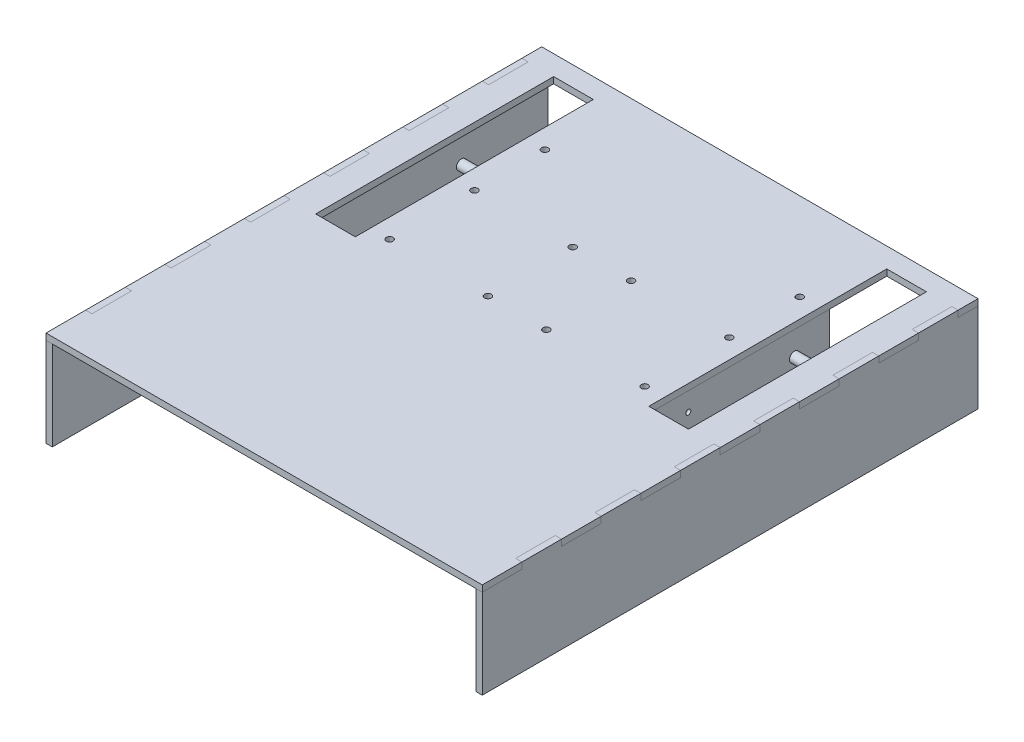
SolidWorks part; units mm, degrees
ref_plane "Front Plane" through (0, 0, 0) normal (0, 0, 1) x (1, 0, 0)
ref_plane "Top Plane" through (0, 0, 0) normal (0, 1, 0) x (1, 0, 0)
ref_plane "Right Plane" through (0, 0, 0) normal (1, 0, 0) x (0, 0, -1)
sketch "Sketch2" plane through (0, 0, 0) normal (0, 1, 0) x (1, 0, 0)
  line L7 (-162.2662, -88.2141) -> (57.7338, -88.2141)
  line L8 (21.7338, 151.7859) -> (41.7338, 151.7859)
  line L9 (57.7338, -88.2141) -> (57.7338, -68.2141)
  line L10 (57.7338, -68.2141) -> (54.5588, -68.2141)
  line L11 (54.5588, -68.2141) -> (54.5588, -48.2141)
  line L12 (54.5588, -48.2141) -> (57.7338, -48.2141)
  line L13 (-162.2662, -88.2141) -> (-162.2662, -68.2141)
  line L14 (-162.2662, -68.2141) -> (-159.0912, -68.2141)
  line L15 (-159.0912, -68.2141) -> (-159.0912, -48.2141)
  line L16 (-159.0912, -48.2141) -> (-162.2662, -48.2141)
  line L17 (-162.2662, -48.2141) -> (-162.2662, -28.2141)
  line L18 (-162.2662, -28.2141) -> (-159.0912, -28.2141)
  line L19 (-159.0912, -28.2141) -> (-159.0912, -8.2141)
  line L20 (-159.0912, -8.2141) -> (-162.2662, -8.2141)
  line L21 (57.7338, -28.2141) -> (54.5588, -28.2141)
  line L22 (54.5588, -28.2141) -> (54.5588, -8.2141)
  line L23 (54.5588, -8.2141) -> (57.7338, -8.2141)
  line L24 (57.7338, -48.2141) -> (57.7338, -28.2141)
  line L25 (-162.2662, -8.2141) -> (-162.2662, 11.7859)
  line L26 (-162.2662, 11.7859) -> (-159.0912, 11.7859)
  line L27 (-159.0912, 11.7859) -> (-159.0912, 31.7859)
  line L28 (-159.0912, 31.7859) -> (-162.2662, 31.7859)
  line L29 (57.7338, 11.7859) -> (54.5588, 11.7859)
  line L30 (54.5588, 11.7859) -> (54.5588, 31.7859)
  line L31 (54.5588, 31.7859) -> (57.7338, 31.7859)
  line L32 (57.7338, -8.2141) -> (57.7338, 11.7859)
  line L33 (-162.2662, 31.7859) -> (-162.2662, 51.7859)
  line L34 (-162.2662, 51.7859) -> (-159.0912, 51.7859)
  line L35 (-159.0912, 51.7859) -> (-159.0912, 71.7859)
  line L36 (-159.0912, 71.7859) -> (-162.2662, 71.7859)
  line L37 (57.7338, 51.7859) -> (54.5588, 51.7859)
  line L38 (54.5588, 51.7859) -> (54.5588, 71.7859)
  line L39 (54.5588, 71.7859) -> (57.7338, 71.7859)
  line L40 (57.7338, 31.7859) -> (57.7338, 51.7859)
  line L45 (21.7338, 151.7859) -> (21.7338, 31.7859)
  line L46 (21.7338, 31.7859) -> (41.7338, 31.7859)
  line L47 (41.7338, 151.7859) -> (41.7338, 31.7859)
  line L48 (-146.2662, 151.7859) -> (-126.2662, 151.7859)
  line L49 (-146.2662, 151.7859) -> (-146.2662, 31.7859)
  line L50 (-146.2662, 31.7859) -> (-126.2662, 31.7859)
  line L51 (-126.2662, 151.7859) -> (-126.2662, 31.7859)
  line L52 (-162.2662, 71.7859) -> (-162.2662, 91.7859)
  line L53 (-162.2662, 91.7859) -> (-159.0912, 91.7859)
  line L54 (-159.0912, 91.7859) -> (-159.0912, 111.7859)
  line L55 (-159.0912, 111.7859) -> (-162.2662, 111.7859)
  line L56 (57.7338, 91.7859) -> (54.5588, 91.7859)
  line L57 (54.5588, 91.7859) -> (54.5588, 111.7859)
  line L58 (54.5588, 111.7859) -> (57.7338, 111.7859)
  line L59 (57.7338, 71.7859) -> (57.7338, 91.7859)
  line L63 (-162.2662, 111.7859) -> (-162.2662, 131.7859)
  line L64 (-162.2662, 131.7859) -> (-159.0912, 131.7859)
  line L65 (-159.0912, 131.7859) -> (-159.0912, 151.7859)
  line L66 (-159.0912, 151.7859) -> (-162.2662, 151.7859)
  line L67 (57.7338, 131.7859) -> (54.5588, 131.7859)
  line L68 (54.5588, 131.7859) -> (54.5588, 151.7859)
  line L69 (54.5588, 151.7859) -> (57.7338, 151.7859)
  line L70 (57.7338, 111.7859) -> (57.7338, 131.7859)
  line L71 (57.7338, 151.7859) -> (57.7338, 161.7859)
  line L72 (57.7338, 161.7859) -> (-162.2662, 161.7859)
  line L73 (-162.2662, 161.7859) -> (-162.2662, 151.7859)
  dimension "D1" = 3.175
  dimension "D2" = 20
  dimension "D3" = 20
  dimension "D4" = 3.175
  dimension "D6" = 220
  dimension "D8" = 20
  dimension "D9" = 20
  dimension "D10" = 16
  dimension "D11" = 16
  dimension "D13" = 120
  dimension "D7" = 10
  dimension "D12" = 10
  dimension "D5" = 6
extrude "Boss-Extrude1" add sketch "Sketch2" along normal blind 3.175
ref_plane "Plane3" through (-52.2662, 0, 0) normal (-1, 0, 0) x (0, 0, 1)
sketch "Sketch3" plane through (-159.0912, 0, 0) normal (-1, 0, 0) x (0, 0, 1)
  line L0 (68.2141, 3.175) -> (68.2141, 0)
  line L1 (68.2141, 0) -> (88.2141, 0)
  line L2 (88.2141, 0) -> (88.2141, -45)
  line L3 (68.2141, 3.175) -> (48.2141, 3.175)
  line L4 (48.2141, 3.175) -> (48.2141, 0)
  line L5 (48.2141, 0) -> (28.2141, 0)
  line L6 (28.2141, 0) -> (28.2141, 3.175)
  line L7 (28.2141, 3.175) -> (8.2141, 3.175)
  line L8 (8.2141, 3.175) -> (8.2141, 0)
  line L9 (8.2141, 0) -> (-11.7859, 0)
  line L10 (-11.7859, 0) -> (-11.7859, 3.175)
  line L11 (-91.7859, 0) -> (-91.7859, 3.175)
  line L12 (-11.7859, 3.175) -> (-31.7859, 3.175)
  line L13 (-31.7859, 3.175) -> (-31.7859, 0)
  line L14 (-31.7859, 0) -> (-51.7859, 0)
  line L15 (-51.7859, 0) -> (-51.7859, 3.175)
  line L16 (-51.7859, 3.175) -> (-71.7859, 3.175)
  line L17 (-71.7859, 3.175) -> (-71.7859, 0)
  line L18 (-71.7859, 0) -> (-91.7859, 0)
  line L21 (-91.7859, 3.175) -> (-111.7859, 3.175)
  line L22 (-111.7859, 3.175) -> (-111.7859, 0)
  line L25 (-111.7859, 0) -> (-131.7859, 0)
  line L26 (-151.7859, 0) -> (-131.7859, 0) construction
  line L27 (-131.7859, 3.175) -> (-131.7859, 0) construction
  line L28 (-131.7859, 0) -> (-131.7859, 3.175)
  line L29 (-131.7859, 3.175) -> (-151.7859, 3.175)
  line L30 (-151.7859, 3.175) -> (-151.7859, 0)
  line L31 (-151.7859, 3.175) -> (-151.7859, 0) construction
  line L32 (-151.7859, 0) -> (-161.732, 0)
  line L33 (-161.732, 0) -> (-161.732, -45)
  line L34 (-161.732, -45) -> (88.2141, -45)
extrude "Boss-Extrude2" add sketch "Sketch3" along normal blind 3.175 separate body
sketch "Sketch4" plane through (0, 0, 0) normal (0, -1, 0) x (1, 0, 0)
  line L0 (-126.2662, -122.8126) -> (-126.2662, -35.4044)
  line L1 (-126.2662, -122.8126) -> (-108.4256, -122.8126)
  line L2 (-126.2662, -35.4044) -> (-108.4256, -35.4044)
  line L4 (-126.2662, -31.7859) -> (-126.2662, -151.7859) construction
  line L5 (-62.765, -35.4044) -> (-62.765, -85.4044)
  line L6 (-62.765, -35.4044) -> (-71.1795, -35.4044)
  line L7 (-62.765, -85.4044) -> (-71.1795, -85.4044)
  line L9 (-108.4256, -35.4044) -> (-108.4256, -55.4044)
  line L10 (-108.4256, -55.4044) -> (-71.1795, -55.4044)
  line L11 (-71.1795, -55.4044) -> (-71.1795, -35.4044)
  line L12 (-71.1795, -85.4044) -> (-71.1795, -65.4044)
  line L13 (-71.1795, -65.4044) -> (-108.4256, -65.4044)
  line L14 (-108.4256, -65.4044) -> (-108.4256, -122.8126)
extrude "Boss-Extrude3" add sketch "Sketch4" along normal blind 1.6129 separate body
sketch "Sketch6" plane through (-126.2662, 113.8349, 0) normal (1, 0, 0) x (0, -1, 0)
  line L0 (115.4478, 35.4044) -> (113.8349, 35.4044)
  line L1 (113.8349, 35.4044) -> (113.8349, 122.8126)
  line L4 (133.4041, 35.4044) -> (115.4478, 35.4044)
  line L7 (135.583, 122.8126) -> (113.8349, 122.8126)
  line L8 (113.8349, 31.7859) -> (113.8349, 151.7859) construction
  line L10 (115.4478, 122.8126) -> (113.8349, 122.8126) construction
  line L11 (135.583, 122.8126) -> (135.583, 85.3092)
  circle A2 centre (133.4041, 73.86) radius 1.27
  arc A3 (133.4041, 35.4044) -> (135.583, 85.3092) centre (133.4041, 60.4044) ccw
  circle A4 centre (133.4041, 51.6858) radius 2.3749
  circle A5 centre (125.8349, 105.2548) radius 2.55
  circle A6 centre (123.1933, 51.6858) radius 1.27
  circle A8 centre (143.6149, 51.6858) radius 1.27
  circle A11 centre (133.4041, 60.4044) radius 17.5692
  point P21 (124.6892, 105.2548)
  point P26 (115.4478, 103.7851)
  dimension "D1" = 5.1
  dimension "D2" = 12
extrude "Boss-Extrude4" add sketch "Sketch6" along normal blind 1.6129
sketch "Sketch7" plane through (0, -1.6129, 0) normal (0, -1, 0) x (1, 0, 0)
  circle A0 centre (-116.5394, -82.125) radius 1.7
  circle A1 centre (-116.5394, -39.3768) radius 1.7
  circle A2 centre (-66.9723, -39.3768) radius 1.7
  circle A3 centre (-66.9723, -82.125) radius 1.7
  circle A4 centre (-116.5394, -117.6269) radius 1.7
  point P1 (-116.5394, -39.3768)
  point P2 (-116.5394, -82.125)
  point P8 (-116.5394, -117.6269)
  dimension "D3" = 3.4
  dimension "D4" = 3.4
  dimension "D5" = 3.4
  dimension "D6" = 3.4
  dimension "D1" = 3.4
extrude "Cut-Extrude1" cut sketch "Sketch7" against normal blind 10
mirror "Mirror1" about plane through (-52.2662, 0, 0) normal (-1, 0, 0) of bodies 157 103 158
mirror "Mirror2" about plane through (-52.2662, 0, 0) normal (-1, 0, 0) of "Cut-Extrude1"
sketch "Sketch9" plane through (-146.2662, 0, 0) normal (1, 0, 0) x (0, 0, -1)
  circle A0 centre (105.2548, -12) radius 2.5
extrude "Boss-Extrude6" add sketch "Sketch9" along normal blind 189 separate body
equation "\"hardboard_width\"= 3.175"
equation "\"D1@Boss-Extrude1\"=\"hardboard_width\""
equation "\"D1@Sketch2\"=\"hardboard_width\""
equation "\"D4@Sketch2\"=\"hardboard_width\""
equation "\"D1@Boss-Extrude2\"=\"hardboard_width\""
equation "\"steel_24g_thickness\"= 0.5"
equation "\"m3_clearance_hole\"= 3.4"
equation "\"D3@Sketch7\"=\"m3_clearance_hole\""
equation "\"D4@Sketch7\"=\"m3_clearance_hole\""
equation "\"D5@Sketch7\"=\"m3_clearance_hole\""
equation "\"D6@Sketch7\"=\"m3_clearance_hole\""
equation "\"steel_16g_thickness\"=1.6129"
equation "\"D1@Boss-Extrude3\"=\"steel_16g_thickness\""
equation "\"D1@Boss-Extrude4\"=\"steel_16g_thickness\""
equation "\"D1@Sketch7\"=\"m3_clearance_hole\""
